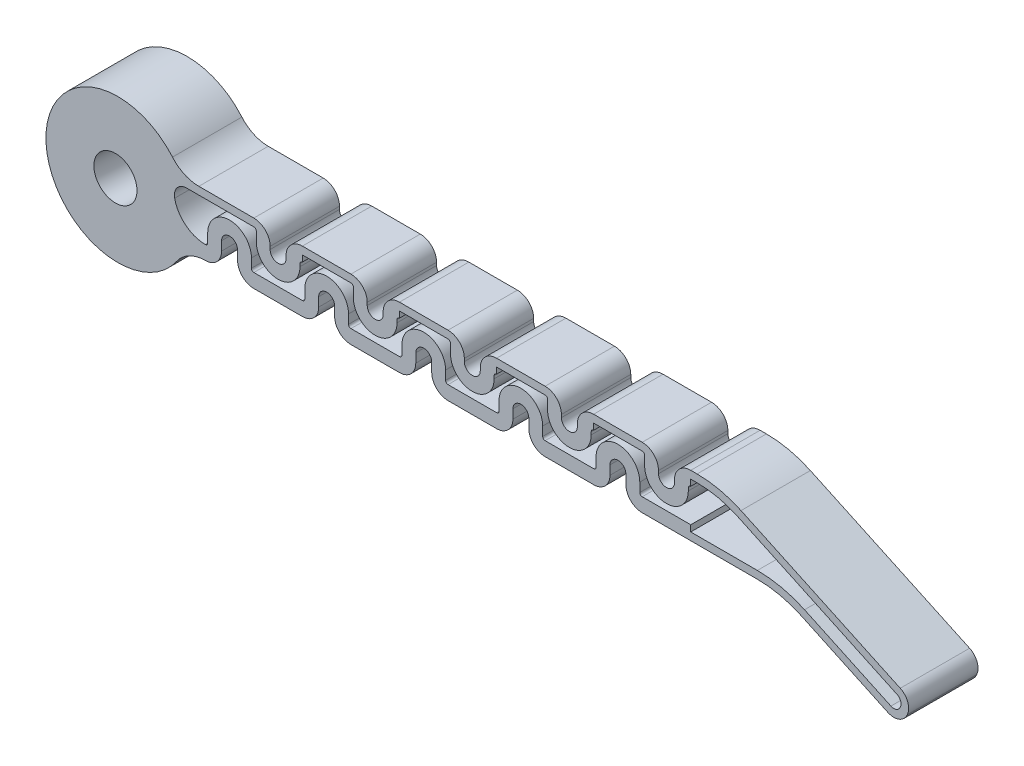
SolidWorks part; units mm, degrees
material "ABS"
ref_plane "Front" through (0, 0, 0) normal (0, 0, 1) x (1, 0, 0)
ref_plane "Top" through (0, 0, 0) normal (0, 1, 0) x (1, 0, 0)
ref_plane "Right" through (0, 0, 0) normal (1, 0, 0) x (0, 0, -1)
sketch "Esquisse1" plane through (0, 0, 0) normal (0, 0, 1) x (1, 0, 0)
  line L2 (9.0907, 5) -> (86.8428, 5)
  line L3 (9.654, -3.8) -> (95.5398, -3.8)
  line L4 (86.8428, 5) -> (114.7214, -8)
  line L5 (114.7214, -8) -> (112.9041, -11.8971)
  line L6 (112.9041, -11.8971) -> (95.5398, -3.8)
  arc A0 (9.0907, 5) -> (9.654, -3.8) centre (0, 0) ccw
  circle A2 centre (0, 0) radius 115 construction
  dimension "D1" = 10.375
  dimension "D4" = 8
  dimension "D5" = 5
  dimension "D9" = 230
  dimension "D2" = 8.8
  dimension "D3" = 4.3
  dimension "D8" = 25
extrude "Boss.-Extru.1" add sketch "Esquisse1" along normal mid plane 10
fillet "Congé4" radius 5 2 edges at (9.654, -3.8, 0) (9.0907, 5, 0)
fillet "Congé3" radius 15 2 edges at (95.5398, -3.8, 0) (86.8428, 5, 0)
sketch "Esquisse10" plane through (0, 0, 0) normal (0, 1, 0) x (1, 0, 0)
  line L0 (0.6976, 9.9756) -> (-0.6976, -9.9756)
  line L1 (-50, 0) -> (50, 0) construction
  line L2 (0.6976, 9.9756) -> (3.79, 9.7594)
  line L3 (3.79, 9.7594) -> (2.3949, -10.1919)
  line L4 (2.3949, -10.1919) -> (-0.6976, -9.9756)
  line L5 (0.6976, 9.9756) -> (0.9138, 13.0681) construction
  dimension "D1" = 86
  dimension "D2" = 20
  dimension "D3" = 6.2
revolve "Enlèvement de matière-Révolution1" cut sketch "Esquisse10" angle 360 about L5
sketch "Esquisse13" plane through (0, 0, 0) normal (0, 0, 1) x (1, 0, 0)
  line L0 (1.9, -6.875) -> (1.9, -10.375)
  line L1 (0, 10.375) -> (3, 10.375)
  line L2 (0, 10.375) -> (0, -10.375)
  line L3 (0, -10.375) -> (1.9, -10.375)
  line L4 (3, 10.375) -> (3, 7.375)
  line L5 (1.9, -6.875) -> (1.55, -6.875)
  line L7 (3, 7.375) -> (1.55, 7.375)
  line L8 (1.55, -6.875) -> (1.55, 7.375)
  line L9 (0, 10.375) -> (0, 13.375) construction
  arc A0 (7.8807, 6.748) -> (8.5075, -5.9382) centre (0, 0) ccw construction
  dimension "D1" = 6
  dimension "D2" = 3.8
  dimension "D3" = 3.1
  dimension "D4" = 3.5
  dimension "D5" = 3
revolve "Enlèvement de matière-Révolution5" [suppressed] cut sketch "Esquisse13" angle 360 about L9
sketch "Esquisse7" plane through (0, 0, 5) normal (0, 0, 1) x (1, 0, 0)
  circle A0 centre (0, 0) radius 10.375
  arc A2 (7.8807, 6.748) -> (8.5075, -5.9382) centre (0, 0) ccw construction
extrude "Boss.-Extru.2" [suppressed] add sketch "Esquisse7" against normal blind 0.2
fillet "Congé5" [suppressed] radius 5
sketch "Esquisse8" plane through (0, 0, -5) normal (0, 0, -1) x (-1, 0, 0)
  line L0 (-17.2576, -0.15) -> (-17.2576, -1.45)
  line L3 (-83.5174, 5) -> (-11.6786, 5) construction
  line L4 (-12.6076, -3.8) -> (-92.2144, -3.8) construction
  line L5 (-19.6076, -3.8) -> (-12.6076, -3.8)
  line L6 (-14.9576, -1.45) -> (-14.9576, -0.15)
  line L8 (-19.6076, 3.9) -> (-12.6076, 3.9)
  line L9 (-12.6076, 3.9) -> (-12.6076, -1.8)
  line L10 (-12.9576, -1.45) -> (-12.9576, -0.15)
  line L11 (-19.2576, -0.15) -> (-19.2576, -1.45)
  line L12 (-19.6076, -1.8) -> (-26.6076, -1.8)
  line L13 (-26.6076, -1.8) -> (-26.6076, 3)
  line L14 (-26.2576, 2.65) -> (-26.2576, 2.25)
  line L15 (-19.9576, 2.25) -> (-19.9576, 3.55)
  line L16 (-26.6076, 5) -> (-19.6076, 5)
  line L17 (-24.2576, 2.65) -> (-24.2576, 2.25)
  line L18 (-21.9576, 2.25) -> (-21.9576, 2.65)
  arc A2 (-17.2576, -1.45) -> (-19.6076, -3.8) centre (-19.6076, -1.45) cw
  arc A3 (-12.6076, -3.8) -> (-14.9576, -1.45) centre (-12.6076, -1.45) cw
  arc A4 (-14.9576, -0.15) -> (-17.2576, -0.15) centre (-16.1076, -0.15) ccw
  arc A5 (-12.6076, -1.8) -> (-12.9576, -1.45) centre (-12.6076, -1.45) cw
  arc A6 (-12.9576, -0.15) -> (-19.2576, -0.15) centre (-16.1076, -0.15) ccw
  arc A7 (-19.2576, -1.45) -> (-19.6076, -1.8) centre (-19.6076, -1.45) cw
  arc A8 (-26.6076, 3) -> (-26.2576, 2.65) centre (-26.6076, 2.65) cw
  arc A9 (-26.2576, 2.25) -> (-19.9576, 2.25) centre (-23.1076, 2.25) ccw
  arc A10 (-19.9576, 3.55) -> (-19.6076, 3.9) centre (-19.6076, 3.55) cw
  arc A11 (-26.6076, 5) -> (-24.2576, 2.65) centre (-26.6076, 2.65) cw
  arc A12 (-24.2576, 2.25) -> (-21.9576, 2.25) centre (-23.1076, 2.25) ccw
  arc A13 (-21.9576, 2.65) -> (-19.6076, 5) centre (-19.6076, 2.65) cw
  dimension "D1" = 2.3
  dimension "D2" = 2
  dimension "D3" = 1.1
  dimension "D4" = 7
  dimension "D5" = 0.9
  dimension "D6" = 70.9098
  dimension "D7" = 14
  dimension "D9" = 0.7
extrude "Enlèv. mat.-Extru.5" cut sketch "Esquisse8" against normal through all and the other way through all
pattern_linear "Répétition linéaire1" count 5 spacing 14 along (1, 0, 0) of "Enlèv. mat.-Extru.5"
sketch "Esquisse9" plane through (0, 0, -5) normal (0, 0, -1) x (-1, 0, 0)
  line L0 (-12.6076, 3.9) -> (-12.6076, -1.8)
  line L1 (-9.9066, 3.9) -> (-12.6076, 3.9)
  line L2 (-9.9066, 2.1399) -> (-8.1862, 1.7683) construction
  line L3 (-83.5174, 3.9) -> (-82.6076, 3.9)
  line L4 (-19.6076, -1.8) -> (-26.6076, -1.8) construction
  line L5 (-82.6076, -1.8) -> (-82.6076, 3) construction
  line L13 (-113.2596, -8.5321) -> (-112.3721, -10.4353)
  line L14 (-112.3721, -10.4353) -> (-99.0185, -4.2084)
  line L15 (-89.3918, 2.5977) -> (-113.2596, -8.5321)
  line L16 (-112.837, -9.4384) -> (-112.7947, -9.529)
  line L17 (-111.4658, -10.0127) -> (-99.0185, -4.2084)
  line L18 (-89.3918, 2.5977) -> (-112.3533, -8.1094)
  line L19 (-92.2144, -2.7) -> (-82.6076, -2.7)
  line L20 (-82.6076, -2.7) -> (-82.6076, 3.9)
  arc A1 (-12.6076, -1.8) -> (-8.1862, 1.7683) centre (-12.6076, 2.7233) ccw
  arc A2 (-8.1862, 1.7683) -> (-9.9066, 3.9) centre (-9.9066, 2.1399) ccw
  arc A3 (-8.5075, -5.9382) -> (-7.8807, 6.748) centre (0, 0) ccw construction
  circle A4 centre (0, 0) radius 8.375 construction
  arc A9 (-112.7947, -9.529) -> (-111.4658, -10.0127) centre (-111.8884, -9.1064) ccw
  arc A10 (-112.837, -9.4384) -> (-112.3533, -8.1094) centre (-111.9307, -9.0157) cw
  arc A11 (-92.2144, -2.7) -> (-99.0185, -4.2084) centre (-92.2144, -18.8) ccw
  arc A12 (-83.5174, 3.9) -> (-89.3918, 2.5977) centre (-83.5174, -10) ccw
  arc A13 (-92.2144, -2.7) -> (-99.0185, -4.2084) centre (-92.2144, -18.8) ccw
  arc A14 (-83.5174, 3.9) -> (-89.3918, 2.5977) centre (-83.5174, -10) ccw
  dimension "D1" = 2
  dimension "D2" = 1.1
  dimension "D3" = 1
extrude "Enlèv. mat.-Extru.6" cut sketch "Esquisse9" against normal through all
fillet "Congé6" radius 2.1 2 edges at (114.7214, -8, 0) (112.9041, -11.8971, 0) tangent propagation no
sketch "Esquisse15" plane through (0, 0, 0) normal (0, 1, 0) x (1, 0, 0)
  line L0 (0, 5) -> (0, -5) construction
  line L1 (150, 5) -> (8.5, 5)
  line L2 (150, 5) -> (150, 1)
  line L3 (150, 1) -> (50, 1)
  line L5 (-10.375, -5) -> (8.5075, -5) construction
  line L6 (8.5075, 5) -> (-10.375, 5) construction
  line L7 (112.8182, -5) -> (89.8567, -5) construction
  ellipse E0 centre (50, 5) end of major axis (8.5, 5) minor radius 4 (8.5, 5) -> (50, 1) ccw
  dimension "D1" = 6
  dimension "D2" = 17
  dimension "D3" = 50
  dimension "D4" = 150
revolve "Enlèvement de matière-Révolution6" [suppressed] cut sketch "Esquisse15" angle 360 about L0
fillet "Congé7" [suppressed] radius 1
sketch "Sketch1" [suppressed] plane through (0, 0, 0) normal (0, 0, 1) x (1, 0, 0)
  circle A0 centre (0, 0) radius 10.375
  dimension "D1" = 20.75
extrude "Cut-Extrude2" [suppressed] cut sketch "Sketch1" against normal through all from offset 4 offset against normal yes
sketch "Sketch2" [suppressed] plane through (0, 0, 0) normal (1, 0, 0) x (0, 0, -1)
  line L1 (3.8113, -10.375) -> (6.8474, -10.375)
  line L2 (3.8113, -10.375) -> (3.8113, 13.3524)
  line L3 (3.8113, 13.3524) -> (6.8474, 13.3524)
  line L4 (6.8474, -10.375) -> (6.8474, 13.3524)
extrude "Cut-Extrude3" [suppressed] cut sketch "Sketch2" against normal through all and the other way blind 10
sketch "Sketch3" [suppressed] plane through (0, 0, -3.8113) normal (0, 0, -1) x (-1, 0, 0)
  circle A0 centre (-5.7385, -6.5818) radius 0.75
  circle A1 centre (-7.2335, -3.4171) radius 0.75
  circle A2 centre (-8.7285, -0.2525) radius 0.75
  circle A3 centre (-6.5818, 5.7385) radius 0.75
  circle A4 centre (-3.4171, 7.2335) radius 0.75
  circle A5 centre (-0.2525, 8.7285) radius 0.75
  circle A6 centre (0.2525, -8.7285) radius 0.75
  circle A7 centre (3.4171, -7.2335) radius 0.75
  circle A8 centre (6.5818, -5.7385) radius 0.75
  circle A9 centre (8.7285, 0.2525) radius 0.75
  circle A10 centre (7.2335, 3.4171) radius 0.75
  circle A11 centre (5.7385, 6.5818) radius 0.75
extrude "Cut-Extrude4" [suppressed] cut sketch "Sketch3" against normal through all
equation "\"D3@Répétition linéaire1\"=\"D7@Esquisse8\""
